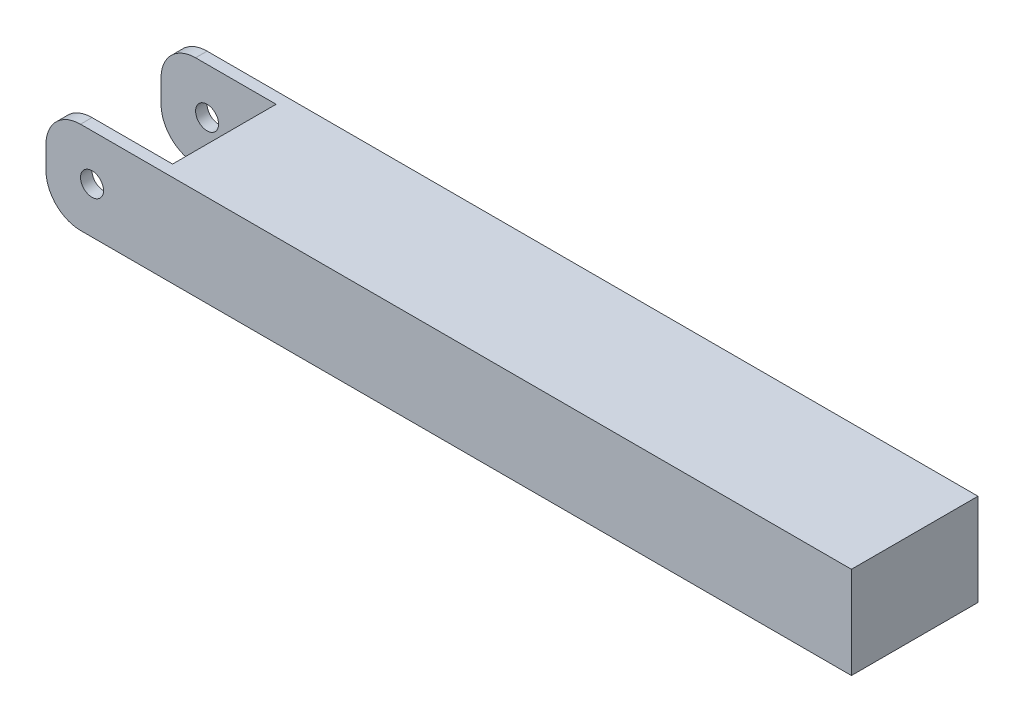
SolidWorks part; units mm, degrees
material "6061-T6 (SS)"
ref_plane "Front Plane" through (0, 0, 0) normal (0, 0, 1) x (1, 0, 0)
ref_plane "Top Plane" through (0, 0, 0) normal (0, 1, 0) x (1, 0, 0)
ref_plane "Right Plane" through (0, 0, 0) normal (1, 0, 0) x (0, 0, -1)
other "Center of Mass"
sketch "Sketch1" plane through (0, 0, 0) normal (0, 0, 1) x (1, 0, 0)
  line L1 (-150, -20) -> (150, -20)
  line L2 (-150, -20) -> (-150, 20)
  line L3 (-150, 20) -> (150, 20)
  line L4 (150, -20) -> (150, 20)
  line L5 (-150, -20) -> (150, 20) construction
  line L6 (-150, 20) -> (150, -20) construction
  point P0 (0, 0)
  dimension "D1" = 40
  dimension "D2" = 300
extrude "Boss-Extrude1" add sketch "Sketch1" along normal mid plane 45
sketch "Sketch2" plane through (0, 0, 22.5) normal (0, 0, 1) x (1, 0, 0)
  line L0 (-150, -20) -> (150, -20) construction
  line L1 (150, 20) -> (-200, 20)
  line L2 (150, 20) -> (150, -20)
  line L3 (150, -20) -> (-200, -20)
  line L4 (-200, 20) -> (-200, -20)
  line L5 (-150, 20) -> (-150, -20) construction
  circle A0 centre (-180, 0) radius 5
  dimension "D2" = 10
  dimension "D1" = 50
  dimension "D3" = 20
extrude "Boss-Extrude2" add sketch "Sketch2" along normal blind 5
fillet "Fillet1" radius 15 2 edges at (-200, -20, 25) (-200, 20, 25)
mirror "Mirror1" about plane through (0, 0, 0) normal (0, 0, 1) of "Fillet1", "Boss-Extrude2"
ref_axis "Axis1" through (-180, 0, 27.5) along (0, 0, -1)
ref_plane "Plane1" through (0, 0, 0) normal (0, 0, 1) x (1, 0, 0)
ref_point "Point2"
